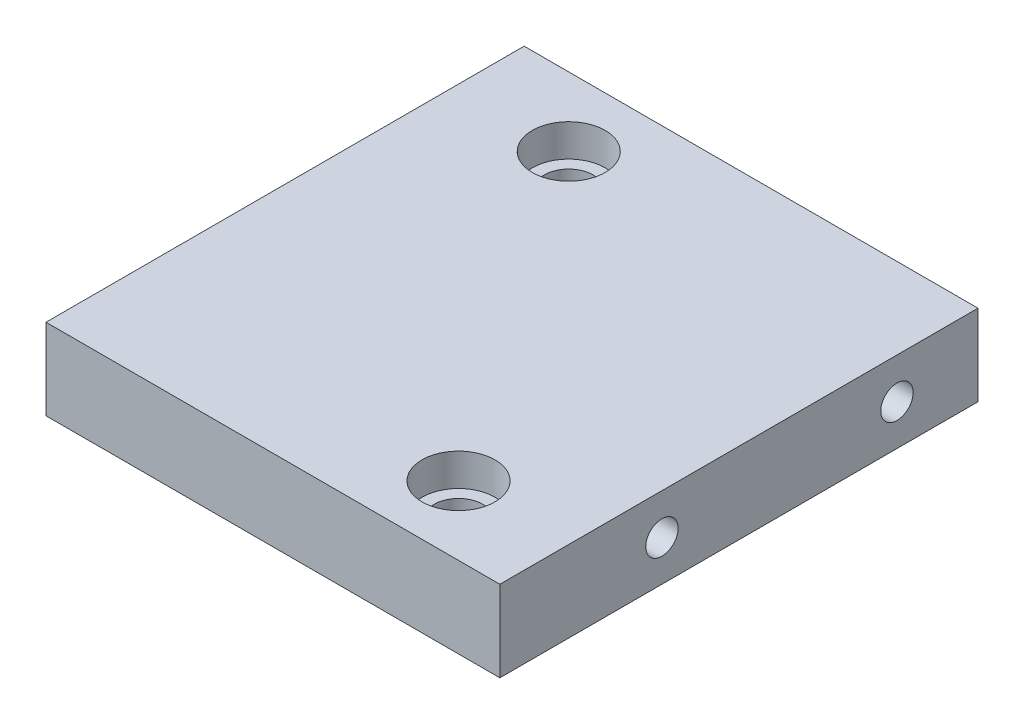
SolidWorks part; units mm, degrees
other "标注1"
sketch "草图3" plane through (0, 5, 29.5) normal (-0.6417, 0.7662, 0.0339) x (0.7661, 0.6384, 0.0747)
ref_plane "前视基准面" through (0, 0, 0) normal (0, 0, 1) x (1, 0, 0)
ref_plane "上视基准面" through (0, 0, 0) normal (0, 1, 0) x (1, 0, 0)
ref_plane "右视基准面" through (0, 0, 0) normal (1, 0, 0) x (0, 0, -1)
other "Configuration Table"
sketch "草图1" plane through (0, 0, 0) normal (0, 1, 0) x (1, 0, 0)
  line L33 (-28, -29.5) -> (0, -29.5)
  line L34 (-28, -29.5) -> (-28, 0)
  line L36 (0, -29.5) -> (0, 0)
  line L37 (-28, 0) -> (0, 0)
  circle A12 centre (-21, -4.25) radius 1.5
  circle A13 centre (-21, -4.25) radius 2.25
  circle A14 centre (-6.8, -25.25) radius 1.5
  circle A15 centre (-6.8, -25.25) radius 2.25
  point P0 (-90.6464, 22.0667)
  dimension "D1" = 28
  dimension "D2" = 29.5
  dimension "D3" = 3
  dimension "D4" = 4.5
extrude "凸台-拉伸1" add sketch "草图1" along normal blind 5 contours L34 | L36 L37 L34 L33
extrude "切除-拉伸1" cut sketch "草图1<20>" along normal through all contours A12 | A14
sketch "草图1<20>" plane through (0, 0, 0) normal (0, 1, 0) x (1, 0, 0) same geometry as "草图1"
extrude "切除-拉伸2" cut sketch "草图1<21>" against normal blind 2 from surface contours A13 | A15 starting at face at (-21, 5, 5.75)
sketch "草图1<21>" plane through (0, 0, 0) normal (0, 1, 0) x (1, 0, 0) same geometry as "草图1"
sketch "草图4" plane through (-28, 0, 0) normal (-1, 0, 0) x (0, 0, 1)
  line L1 (0, 5) -> (0, 0) construction
  line L2 (29.5, 5) -> (29.5, 0) construction
  circle A0 centre (5, 2.5) radius 1
  circle A1 centre (19.5, 2.5) radius 1
  point P9 (0, 2.5)
  dimension "D1" = 2
  dimension "D2" = 5
  dimension "D3" = 10
extrude "切除-拉伸3" cut sketch "草图4" along normal blind 4 from surface starting at face at (0, 2.5, 14.75)
